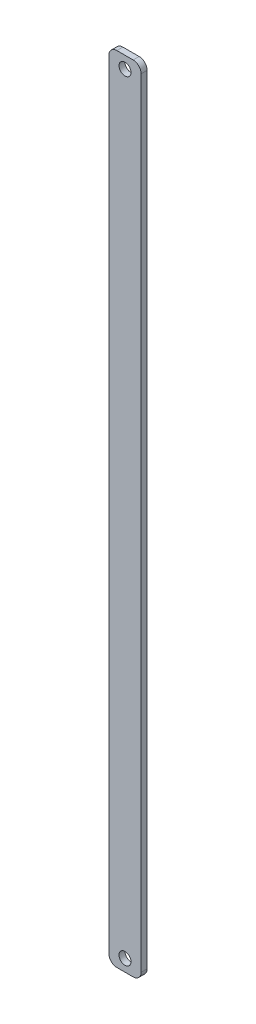
SolidWorks part; units mm, degrees
ref_plane "Front Plane" through (0, 0, 0) normal (0, 0, 1) x (1, 0, 0)
ref_plane "Top Plane" through (0, 0, 0) normal (0, 1, 0) x (1, 0, 0)
ref_plane "Right Plane" through (0, 0, 0) normal (1, 0, 0) x (0, 0, -1)
sketch "Sketch1" plane through (0, 0, 0) normal (0, 1, 0) x (1, 0, 0)
  line L1 (-4.03, -0.75) -> (4.03, -0.75)
  line L2 (-4.03, -0.75) -> (-4.03, 0.75)
  line L3 (-4.03, 0.75) -> (4.03, 0.75)
  line L4 (4.03, -0.75) -> (4.03, 0.75)
  line L5 (-4.03, -0.75) -> (4.03, 0.75) construction
  line L6 (-4.03, 0.75) -> (4.03, -0.75) construction
  point P0 (0, 0)
  dimension "D1" = 8.06
  dimension "D2" = 1.5
extrude "Boss-Extrude1" add sketch "Sketch1" along normal blind 198.5
sketch "Sketch2" plane through (0, 0, 0.75) normal (0, 0, 1) x (1, 0, 0)
  line L0 (-4.03, 198.5) -> (-4.03, 0) construction
  line L1 (4.03, 99.25) -> (-4.03, 99.25) construction
  line L2 (4.03, 198.5) -> (4.03, 0) construction
  circle A0 centre (0, 3) radius 1.5
  circle A1 centre (0, 195.5) radius 1.5
  dimension "D2" = 3
  dimension "D1" = 3
  dimension "D3" = 4.03
extrude "Cut-Extrude1" cut sketch "Sketch2" against normal up to surface (1.5 mm away) up to face at (0, 99.25, -0.75)
fillet "Fillet1" radius 2 4 edges at (-4.03, 0, 0) (4.03, 0, 0) (-4.03, 198.5, 0) (4.03, 198.5, 0)
